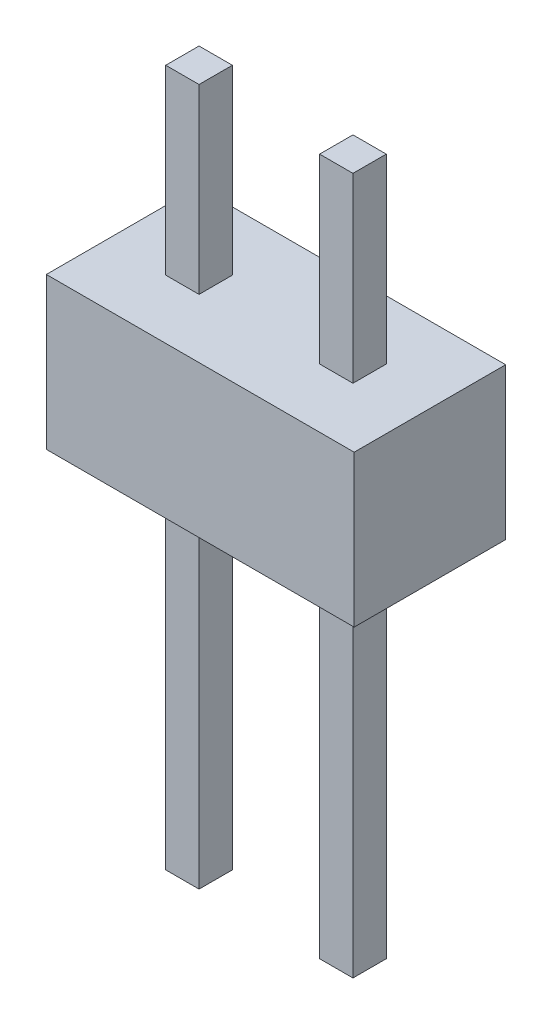
SolidWorks part; units mm, degrees
ref_plane "Front Plane" through (0, 0, 0) normal (0, 0, 1) x (1, 0, 0)
ref_plane "Top Plane" through (0, 0, 0) normal (0, 1, 0) x (1, 0, 0)
ref_plane "Right Plane" through (0, 0, 0) normal (1, 0, 0) x (0, 0, -1)
sketch "Sketch1" plane through (0, 0, 0) normal (0, 0, 1) x (1, 0, 0)
  line L1 (0, 0) -> (5.08, 0)
  line L2 (0, 0) -> (0, 2.5)
  line L3 (0, 2.5) -> (5.08, 2.5)
  line L4 (5.08, 0) -> (5.08, 2.5)
  dimension "D1" = 2.5
  dimension "D2" = 5.08
extrude "Boss-Extrude1" add sketch "Sketch1" along normal mid plane 2.5
sketch "Sketch2" plane through (0, 0, 0) normal (0, -1, 0) x (1, 0, 0)
  line L0 (0, 0) -> (5.08, 0) construction
  line L1 (5.08, 1.25) -> (5.08, -1.25) construction
  line L2 (3.535, -0.275) -> (4.085, -0.275)
  line L3 (0.995, -0.275) -> (1.545, -0.275)
  line L4 (0.995, -0.275) -> (0.995, 0.275)
  line L5 (0.995, 0.275) -> (1.545, 0.275)
  line L6 (1.545, -0.275) -> (1.545, 0.275)
  line L7 (0.995, -0.275) -> (1.545, 0.275) construction
  line L8 (0.995, 0.275) -> (1.545, -0.275) construction
  line L9 (3.535, -0.275) -> (3.535, 0.275)
  line L10 (3.535, 0.275) -> (4.085, 0.275)
  line L11 (4.085, -0.275) -> (4.085, 0.275)
  line L12 (3.535, -0.275) -> (4.085, 0.275) construction
  line L13 (3.535, 0.275) -> (4.085, -0.275) construction
  line L14 (1.27, 0) -> (3.81, 0) construction
  point P5 (1.27, 0)
  point P12 (3.81, 0)
  dimension "D1" = 0.55
  dimension "D3" = 1.27
  dimension "D4" = 2.54
  dimension "D2" = 2
extrude "Boss-Extrude2" add sketch "Sketch2" along normal blind 6 separate body
ref_axis "Axis1" through (1.27, 0, 0) along (0, -1, 0)
ref_axis "Axis2" through (3.81, 0, 0) along (0, -1, 0)
extrude "Boss-Extrude3" add sketch "Sketch2<2>" against normal blind 5.5 separate body
sketch "Sketch2<2>" plane through (0, 0, 0) normal (0, -1, 0) x (1, 0, 0) same geometry as "Sketch2"
